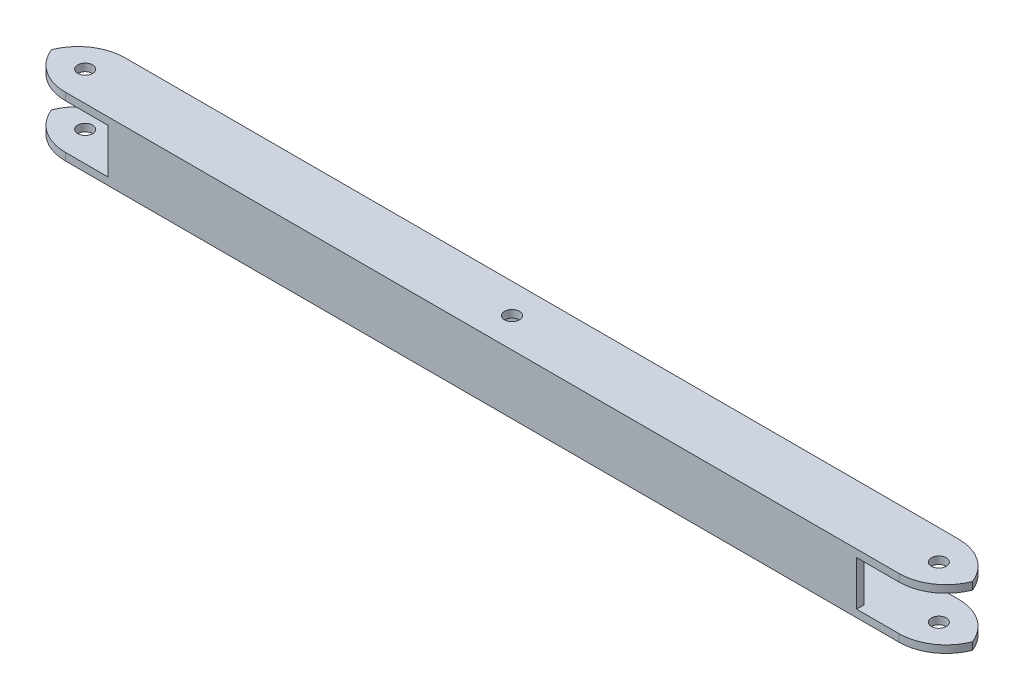
SolidWorks part; units mm, degrees
ref_plane "Front Plane" through (0, 0, 0) normal (0, 0, 1) x (1, 0, 0)
ref_plane "Top Plane" through (0, 0, 0) normal (0, 1, 0) x (1, 0, 0)
ref_plane "Right Plane" through (0, 0, 0) normal (1, 0, 0) x (0, 0, -1)
sketch "Sketch1" plane through (0, 0, 0) normal (0, 1, 0) x (1, 0, 0)
  line L0 (0, 0) -> (395.5, 0)
  line L1 (395.5, 0) -> (395.5, -25.4)
  line L2 (395.5, -25.4) -> (0, -25.4)
  line L3 (0, -25.4) -> (0, 0)
  line L4 (197.75, 0) -> (197.75, -25.4) construction
  line L5 (0, -12.7) -> (395.5, -12.7) construction
  circle A3 centre (197.75, -12.7) radius 3.175
  circle A6 centre (15.76, -12.7) radius 3.175
  circle A8 centre (379.74, -12.7) radius 3.175
  circle A9 centre (15.76, -12.7) radius 3.175 construction
  dimension "D3" = 6.35
  dimension "D5" = 181.99
  dimension "D4" = 6.35
  dimension "D1" = 395.5
  dimension "D2" = 25.4
extrude "Boss-Extrude1" add sketch "Sketch1" along normal blind 25.4
sketch "Sketch2" plane through (0, 0, 0) normal (-1, 0, 0) x (0, 0, 1)
  line L14 (3.175, 22.225) -> (3.175, 3.175)
  line L15 (3.175, 3.175) -> (22.225, 3.175)
  line L16 (22.225, 3.175) -> (22.225, 22.225)
  line L17 (22.225, 22.225) -> (3.175, 22.225)
  line L18 (3.175, 22.225) -> (3.175, 3.175)
  line L19 (3.175, 3.175) -> (22.225, 3.175)
  line L20 (22.225, 3.175) -> (22.225, 22.225)
  line L21 (22.225, 22.225) -> (3.175, 22.225)
  dimension "D1" = 3.175
extrude "Cut-Extrude1" cut sketch "Sketch2" against normal up to surface (395.5 mm away) up to face at (395.5, 12.7, 12.7)
sketch "Sketch4" plane through (0, 0, 0) normal (-1, 0, 0) x (0, 0, 1)
  line L1 (25.4, 25.4) -> (25.4, 0) construction
  line L2 (25.4, 22.225) -> (25.4, 3.175)
  line L3 (25.4, 3.175) -> (0, 3.175)
  line L4 (0, 25.4) -> (0, 0) construction
  line L5 (0, 3.175) -> (0, 22.225)
  line L7 (0, 22.225) -> (25.4, 22.225)
  line L8 (0, 25.4) -> (25.4, 25.4) construction
  line L9 (3.175, 3.175) -> (22.225, 3.175) construction
  dimension "D2" = 3.175
extrude "Cut-Extrude2" cut sketch "Sketch4" against normal blind 38.1
ref_plane "Plane1" through (197.75, 0, 0) normal (-1, 0, 0) x (0, 0, 1)
mirror "Mirror1" about plane through (197.75, 0, 0) normal (-1, 0, 0) of "Cut-Extrude2"
fillet "Fillet1" radius 20 8 edges at (395.5, 1.5875, 0) (395.5, 23.8125, 0) (395.5, 1.5875, 25.4) (395.5, 23.8125, 25.4) (0, 1.5875, 25.4) (0, 23.8125, 25.4) (0, 1.5875, 0) (0, 23.8125, 0)
sketch "Sketch5" plane through (0, 25.4, 0) normal (0, 1, 0) x (1, 0, 0)
  circle A0 centre (15.76, -12.7) radius 3.175 construction
  circle A1 centre (379.74, -12.7) radius 3.175 construction
